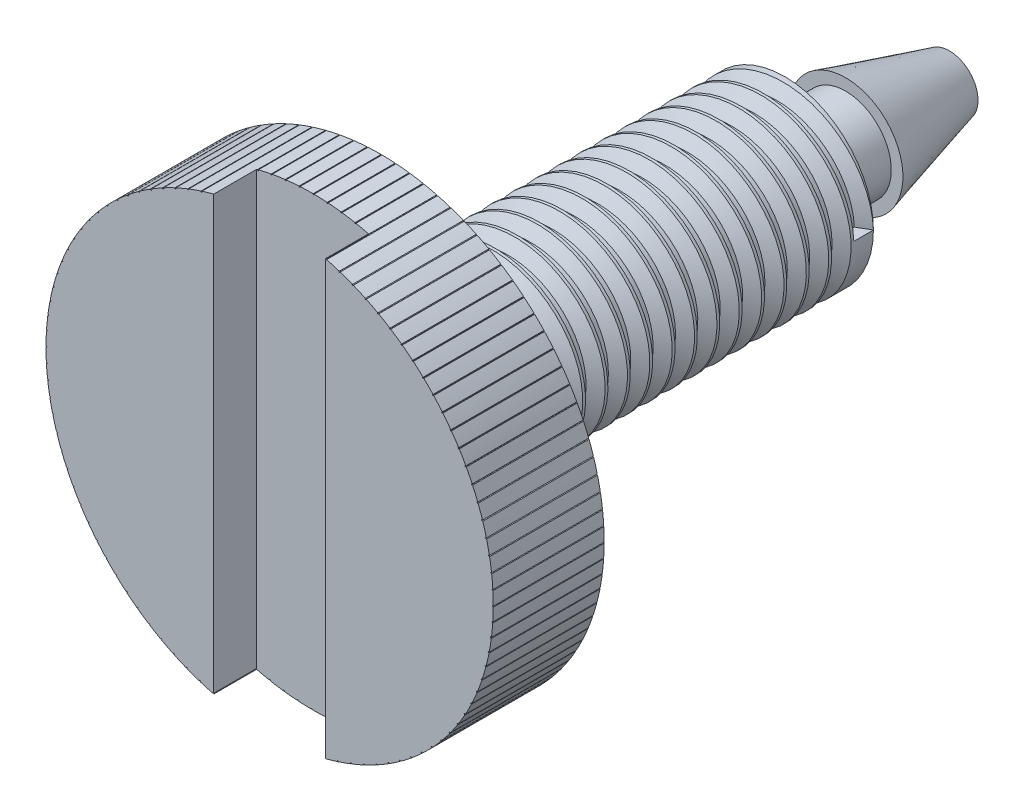
SolidWorks part; units mm, degrees
material "Brass"
ref_plane "Front Plane" through (0, 0, 0) normal (0, 0, 1) x (1, 0, 0)
ref_plane "Top Plane" through (0, 0, 0) normal (0, 1, 0) x (1, 0, 0)
ref_plane "Right Plane" through (0, 0, 0) normal (1, 0, 0) x (0, 0, -1)
sketch "Sketch1" plane through (0, 0, 0) normal (0, 1, 0) x (1, 0, 0)
  line L0 (0, 0) -> (3.175, 0)
  line L1 (3.175, 0) -> (3.175, 1.5748)
  line L2 (3.175, 1.5748) -> (1.2573, 1.5748)
  line L3 (1.2573, 1.5748) -> (1.2573, 7.3152)
  line L4 (1.2573, 7.3152) -> (0.6477, 7.3152)
  line L7 (0, 9.652) -> (0, 0) construction
  line L8 (0, 0) -> (0, 9.652)
  line L10 (0.6477, 7.3152) -> (0.6477, 8.1788)
  line L13 (0.6477, 8.1788) -> (0.8128, 8.1788)
  line L14 (0.8128, 8.1788) -> (0.4064, 9.652)
  line L15 (0, 9.652) -> (0.4064, 9.652)
  dimension "D1" = 3.175
  dimension "D2" = 0.6096
  dimension "D3" = 0.4064
  dimension "D4" = 9.652
  dimension "D5" = 1.5748
  dimension "D6" = 1.2573
  dimension "D7" = 5.7404
  dimension "D8" = 0.8636
  dimension "D9" = 0.1651
revolve "Revolve1" add sketch "Sketch1" angle 360 about L7
cosmetic thread "Cosmetic Thread2" parameters "D2"=1.1455
sketch "Sketch2" plane through (0, 0, 0) normal (0, 1, 0) x (1, 0, 0)
  line L1 (-0.7937, -0.6096) -> (0.7938, -0.6096)
  line L2 (-0.7937, -0.6096) -> (-0.7937, 0.6096)
  line L3 (-0.7937, 0.6096) -> (0.7938, 0.6096)
  line L4 (0.7938, -0.6096) -> (0.7938, 0.6096)
  line L5 (-0.7937, -0.6096) -> (0.7938, 0.6096) construction
  line L6 (-0.7937, 0.6096) -> (0.7938, -0.6096) construction
  point P0 (0, 0)
  dimension "D1" = 1.5875
  dimension "D2" = 1.2192
extrude "Cut-Extrude1" cut sketch "Sketch2" against normal mid plane 12.7
thread "Thread1" pitch 0.3175 method cut profile "Thread Profile1" start angle 0, offset 0, length 4.318, pitch 0.3175, diameter 2.5146
ref_plane "Plane1" through (1.2573, 0, -7.3152) normal (0, -1, 0) x (1, 0, 0)
sketch "Thread Profile1" plane through (1.2573, 0, -7.3152) normal (0, -1, 0) x (1, 0, 0)
  line L0 (0, 0) -> (0, 0.3175) construction
  line L11 (0, 0) -> (0, 0.2778)
  line L12 (0, 0.2778) -> (-0.1719, 0.1786)
  line L13 (-0.1719, 0.1786) -> (-0.1719, 0.0992)
  line L15 (-0.1719, 0.0992) -> (0, 0)
  line L17 (-0.1719, 0.1389) -> (0, 0.1389) construction
  point P2 (0, 0)
  dimension "Pitch" = 0.3175
  dimension "Profile_Angle" = 60
  dimension "Profile_Land" = 0.0794
  dimension "Profile_Height" = 0.1719
cosmetic thread "Cosmetic Thread1" parameters "D2"=1.5146
cosmetic thread "Cosmetic Thread3" parameters "D2"=1.1455
cosmetic thread "Cosmetic Thread4" parameters "D2"=1.1455
sketch "Sketch9" plane through (0, 0, -1.5748) normal (0, 0, -1) x (-1, 0, 0)
  line L1 (-2.9446, 1.1491) -> (-2.9604, 1.1491)
  line L2 (-2.9446, 1.1491) -> (-2.9446, 1.1612)
  line L3 (-2.9446, 1.1612) -> (-2.9604, 1.1612)
  line L4 (-2.9604, 1.1491) -> (-2.9604, 1.1612)
extrude "Cut-Extrude4" cut sketch "Sketch9" against normal through all
pattern_circular "CirPattern1" count 100 over 360 about axis through (0, 0, -9.652) along (0, 0, -1) of "Cut-Extrude4"
